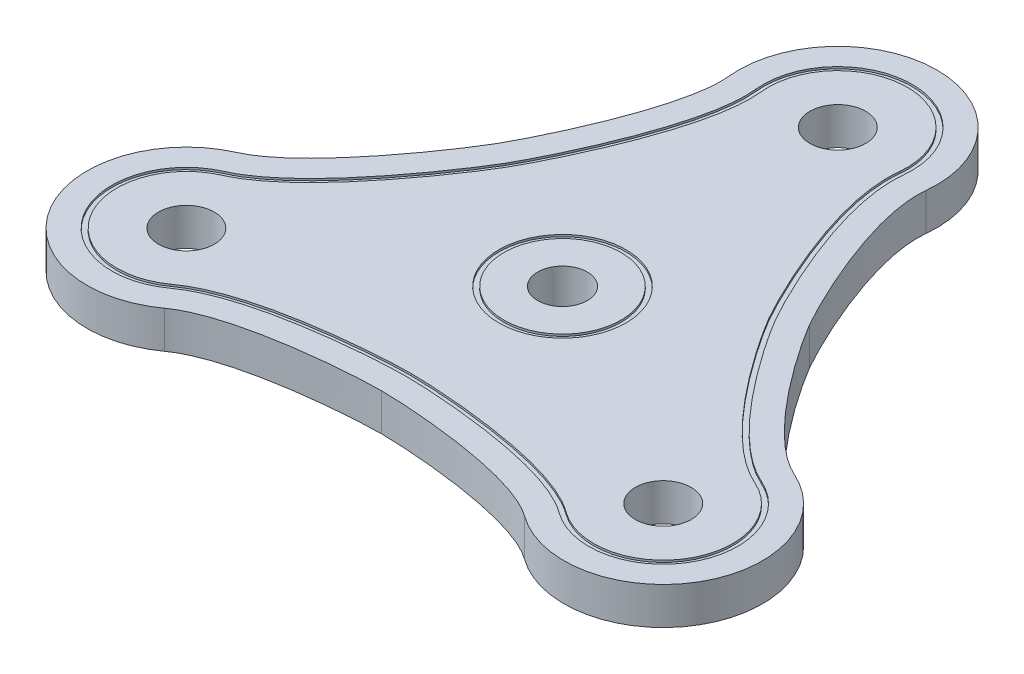
SolidWorks part; units mm, degrees
ref_plane "Front Plane" through (0, 0, 0) normal (0, 0, 1) x (1, 0, 0)
ref_plane "Top Plane" through (0, 0, 0) normal (0, 1, 0) x (1, 0, 0)
ref_plane "Right Plane" through (0, 0, 0) normal (1, 0, 0) x (0, 0, -1)
sketch "Sketch1" plane through (0, 0, 0) normal (0, 1, 0) x (1, 0, 0)
  line L0 (0, 35.2219) -> (0, 0) construction
  line L1 (0, 0) -> (-30.503, -17.6109) construction
  line L2 (0, 0) -> (30.503, -17.6109) construction
  line L3 (0, 35.2219) -> (0, 69.7598) construction
  line L4 (-30.503, -17.6109) -> (-60.4137, -34.8799) construction
  line L5 (30.503, -17.6109) -> (60.4137, -34.8799) construction
  line L6 (-30.503, -17.6109) -> (0, 35.2219) construction
  line L7 (0, 35.2219) -> (30.503, -17.6109) construction
  line L8 (30.503, -17.6109) -> (-30.503, -17.6109) construction
  line L9 (52.5001, -30.3109) -> (-52.5001, -30.3109)
  line L10 (-52.5001, -30.3109) -> (0, 60.6219)
  line L11 (0, 60.6219) -> (52.5001, -30.3109)
  circle A0 centre (-30.503, -17.6109) radius 7.1232 construction
  circle A1 centre (0, 35.2219) radius 7.1232 construction
  circle A2 centre (30.503, -17.6109) radius 7.1232 construction
  circle A3 centre (0, 0) radius 3.175
  dimension "D3" = 61.0061
  dimension "D5" = 6.35
  dimension "D1" = 120
  dimension "D2" = 120
  dimension "D4" = 12.7
extrude "Boss-Extrude1" add sketch "Sketch1" along normal blind 4.7752
fillet "Fillet1" radius 12.7 3 edges at (52.5001, 2.3876, 30.3109) (0, 2.3876, -60.6219) (-52.5001, 2.3876, 30.3109)
hole_wizard "1/4 Clearance Hole1" positions "Sketch5" profile "Sketch4" hole size "1/4" standard "ANSI Inch"
sketch "Sketch5" plane through (0, 4.7752, 0) normal (0, 1, 0) x (1, 0, 0)
  point P0 (0, 35.2219)
  point P3 (-30.503, -17.6109)
  point P6 (30.503, -17.6109)
sketch "Sketch4" plane through (0, 4.7752, -35.2219) normal (1, 0, 0) x (0, 0, 1)
  line L0 (0, 0) -> (0, 37.1978)
  line L1 (0, 37.1978) -> (3.5712, 35.052)
  line L2 (3.5712, 35.052) -> (3.5712, 0)
  line L5 (3.5712, 0) -> (0, 0)
  line L10 (0, 37.1978) -> (-3.5712, 35.052) construction
  line L11 (0, -6.35) -> (0, 107.95) construction
  dimension "Hole Dia." = 7.1425
  dimension "Hole Depth" = 35.052
  dimension "Drill Angle" = 118
ref_axis "Axis1" through (0, 12.9178, 0) along (0, -1, 0)
sketch "Sketch8" plane through (0, 0, 0) normal (0, 1, 0) x (1, 0, 0)
  line L0 (26.25, 15.1555) -> (20.0453, 11.5732) construction
  line L1 (0, 60.6219) -> (52.5001, -30.3109) construction
  line L2 (41.5015, -11.2609) -> (10.9985, 41.5719)
  circle A0 centre (0, 35.2219) radius 12.7
  arc A1 (10.9985, 41.5719) -> (-10.9985, 41.5719) centre (0, 35.2219) ccw construction
  circle A2 centre (30.503, -17.6109) radius 12.7
  spline S0 degree 3 poles (20.0453, 11.5732) (18.0567, 15.0175) (11.9581, 27.5448) (12.6294, 33.8846) knots 0 0 0 0 1 1 1 1
  spline S1 degree 3 poles (20.0453, 11.5732) (22.0339, 8.1288) (29.8336, -3.4164) (35.6596, -6.0049) knots 0 0 0 0 1 1 1 1
extrude "Cut-Extrude3" cut sketch "Sketch8" along normal through all contours L0 L2 A0 S0 | L2 L0 S1 A2 region at (29.081, 0, -4.4076) region at (18.3576, 0, -22.9811)
pattern_circular "CirPattern6" count 3 over 360 about axis through (0, 12.9178, 0) along (0, -1, 0) of "Cut-Extrude3"
sketch "Sketch9" plane through (0, 4.7752, 0) normal (0, 1, 0) x (1, 0, 0)
  arc A0 (9.472, 34.2189) -> (-9.472, 34.2189) centre (0, 35.2219) ccw
  arc A1 (-34.3705, -8.9064) -> (-24.8984, -25.3125) centre (-30.503, -17.6109) ccw
  arc A2 (24.8984, -25.3125) -> (34.3705, -8.9064) centre (30.503, -17.6109) ccw
  arc A3 (12.6294, 33.8846) -> (-12.6294, 33.8846) centre (0, 35.2219) ccw
  arc A4 (-35.6596, -6.0049) -> (-23.0302, -27.8797) centre (-30.503, -17.6109) ccw
  arc A5 (23.0302, -27.8797) -> (35.6596, -6.0049) centre (30.503, -17.6109) ccw
  arc A6 (12.6294, 33.8846) -> (-12.6294, 33.8846) centre (0, 35.2219) ccw construction
  arc A7 (-35.6596, -6.0049) -> (-23.0302, -27.8797) centre (-30.503, -17.6109) ccw construction
  arc A8 (23.0302, -27.8797) -> (35.6596, -6.0049) centre (30.503, -17.6109) ccw construction
  arc A9 (8.8406, 34.2858) -> (-8.8406, 34.2858) centre (0, 35.2219) ccw
  arc A10 (-34.1126, -9.4867) -> (-25.2721, -24.7991) centre (-30.503, -17.6109) ccw
  arc A11 (25.2721, -24.7991) -> (34.1126, -9.4867) centre (30.503, -17.6109) ccw
  circle A12 centre (0, 0) radius 7.4922
  circle A13 centre (0, 0) radius 8.1272
  spline S0 degree 1 poles (-9.472, 34.2189) (-17.2957, 9.9857) knots 0 0 1 1 construction
  spline S1 degree 1 poles (-17.2957, 9.9857) (-34.3705, -8.9064) knots 0 0 1 1 construction
  spline S2 degree 1 poles (-24.8984, -25.3125) (0, -19.9713) knots 0 0 1 1 construction
  spline S3 degree 1 poles (0, -19.9713) (24.8984, -25.3125) knots 0 0 1 1 construction
  spline S4 degree 1 poles (34.3705, -8.9064) (17.2957, 9.9857) knots 0 0 1 1 construction
  spline S5 degree 1 poles (17.2957, 9.9857) (9.472, 34.2189) knots 0 0 1 1 construction
  spline S6 degree 3 poles (-1302.6575, -1493.3617) (1264.2656, 1760.3115) (-1222.2453, -1769.2494) (1055.4921, 1697.5307) knots -4.35176 -4.35176 -4.35176 -4.35176 5.311596 5.311596 5.311596 5.311596 only from (-12.6294, 33.8846) to (-20.0453, 11.5732)
  spline S7 degree 3 poles (-942.3647, -1762.8603) (921.0943, 1943.1248) (-892.3396, -1975.0381) (641.9557, 1874.8036) knots -4.311607 -4.311607 -4.311607 -4.311607 5.35175 5.35175 5.35175 5.35175 only from (-20.0453, 11.5732) to (-35.6596, -6.0049)
  spline S8 degree 3 poles (1944.6179, -381.4536) (-2156.6073, 214.7304) (2143.3376, -173.8708) (-1997.8508, 65.3176) knots -4.35176 -4.35176 -4.35176 -4.35176 5.311596 5.311596 5.311596 5.311596 only from (-23.0302, -27.8797) to (0, -23.1463)
  spline S9 degree 3 poles (1997.8642, 65.3184) (-2143.3426, -173.8714) (2156.603, 214.7302) (-1944.6054, -381.4518) knots -4.311607 -4.311607 -4.311607 -4.311607 5.35175 5.35175 5.35175 5.35175 only from (0, -23.1463) to (23.0302, -27.8797)
  spline S10 degree 3 poles (-641.9604, 1874.8154) (892.3417, -1975.0419) (-921.0923, 1943.1202) (942.3587, -1762.8483) knots -4.35176 -4.35176 -4.35176 -4.35176 5.311596 5.311596 5.311596 5.311596 only from (35.6596, -6.0049) to (20.0453, 11.5732)
  spline S11 degree 3 poles (-1055.4995, 1697.5419) (1222.2483, -1769.2535) (-1264.2633, 1760.3078) (1302.6497, -1493.3518) knots -4.311607 -4.311607 -4.311607 -4.311607 5.35175 5.35175 5.35175 5.35175 only from (20.0453, 11.5732) to (12.6294, 33.8846)
  spline S12 degree 3 poles (-12.6294, 33.8846) (-11.9581, 27.5448) (-18.0567, 15.0175) (-20.0453, 11.5732) knots 0 0 0 0 1 1 1 1 construction
  spline S13 degree 3 poles (-20.0453, 11.5732) (-22.0339, 8.1288) (-29.8336, -3.4164) (-35.6596, -6.0049) knots 0 0 0 0 1 1 1 1 construction
  spline S14 degree 3 poles (-23.0302, -27.8797) (-17.8754, -24.1284) (-3.9772, -23.1463) (0, -23.1463) knots 0 0 0 0 1 1 1 1 construction
  spline S15 degree 3 poles (0, -23.1463) (3.9772, -23.1463) (17.8754, -24.1284) (23.0302, -27.8797) knots 0 0 0 0 1 1 1 1 construction
  spline S16 degree 3 poles (35.6596, -6.0049) (29.8336, -3.4164) (22.0339, 8.1288) (20.0453, 11.5732) knots 0 0 0 0 1 1 1 1 construction
  spline S17 degree 3 poles (20.0453, 11.5732) (18.0567, 15.0175) (11.9581, 27.5448) (12.6294, 33.8846) knots 0 0 0 0 1 1 1 1 construction
  spline S18 degree 3 poles (-9.472, 34.2189) (-9.3554, 33.1172) (-9.4289, 30.9191) (-10.0752, 27.4819) (-11.0973, 23.9595) (-12.3605, 20.4654) (-13.7396, 17.1479) (-14.8823, 14.664) (-15.7312, 12.9274) (-16.3214, 11.7688) (-16.7608, 10.9422) (-17.0807, 10.3623) (-17.2215, 10.1142) (-17.2957, 9.9857) knots 0 0 0 0 0.125 0.25 0.375 0.5 0.625 0.75 0.8125 0.875 0.9375 0.96875 1 1 1 1
  spline S19 degree 3 poles (-17.2957, 9.9857) (-17.3699, 9.8572) (-17.5144, 9.6112) (-17.8566, 9.0442) (-18.3528, 8.2503) (-19.0611, 7.1599) (-20.1405, 5.5564) (-21.7203, 3.3249) (-23.9038, 0.4718) (-26.2982, -2.3692) (-28.8376, -5.0156) (-31.4912, -7.2939) (-33.3581, -8.4566) (-34.3705, -8.9064) knots 0 0 0 0 0.03125 0.0625 0.125 0.1875 0.25 0.375 0.5 0.625 0.75 0.875 1 1 1 1
  spline S20 degree 3 poles (-24.8984, -25.3125) (-24.0027, -24.6606) (-22.0623, -23.6252) (-18.7624, -22.4663) (-15.2009, -21.5904) (-11.5433, -20.9372) (-7.9807, -20.4728) (-5.2583, -20.2204) (-3.3299, -20.0874) (-2.0314, -20.0192) (-1.0958, -19.9864) (-0.4337, -19.9735) (-0.1484, -19.9713) (0, -19.9713) knots 0 0 0 0 0.125 0.25 0.375 0.5 0.625 0.75 0.8125 0.875 0.9375 0.96875 1 1 1 1
  spline S21 degree 3 poles (0, -19.9713) (0.1484, -19.9713) (0.4337, -19.9735) (1.0958, -19.9864) (2.0314, -20.0192) (3.3299, -20.0874) (5.2583, -20.2204) (7.9807, -20.4728) (11.5433, -20.9372) (15.2009, -21.5904) (18.7624, -22.4663) (22.0623, -23.6252) (24.0027, -24.6606) (24.8984, -25.3125) knots 0 0 0 0 0.03125 0.0625 0.125 0.1875 0.25 0.375 0.5 0.625 0.75 0.875 1 1 1 1
  spline S22 degree 3 poles (34.3705, -8.9064) (33.3581, -8.4566) (31.4912, -7.2939) (28.8376, -5.0156) (26.2982, -2.3692) (23.9038, 0.4718) (21.7203, 3.3249) (20.1405, 5.5564) (19.0611, 7.1599) (18.3528, 8.2503) (17.8566, 9.0442) (17.5144, 9.6112) (17.3699, 9.8572) (17.2957, 9.9857) knots 0 0 0 0 0.125 0.25 0.375 0.5 0.625 0.75 0.8125 0.875 0.9375 0.96875 1 1 1 1
  spline S23 degree 3 poles (17.2957, 9.9857) (17.2215, 10.1142) (17.0807, 10.3623) (16.7608, 10.9422) (16.3214, 11.7688) (15.7312, 12.9274) (14.8823, 14.664) (13.7396, 17.1479) (12.3605, 20.4654) (11.0973, 23.9595) (10.0752, 27.4819) (9.4289, 30.9191) (9.3554, 33.1172) (9.472, 34.2189) knots 0 0 0 0 0.03125 0.0625 0.125 0.1875 0.25 0.375 0.5 0.625 0.75 0.875 1 1 1 1
  spline S24 degree 1 poles (16.7458, 9.6682) (8.8406, 34.2858) knots 0 0 1 1 construction
  spline S25 degree 1 poles (-8.8406, 34.2858) (-16.7458, 9.6682) knots 0 0 1 1 construction
  spline S26 degree 1 poles (-16.7458, 9.6682) (-34.1126, -9.4867) knots 0 0 1 1 construction
  spline S27 degree 1 poles (-25.2721, -24.7991) (0, -19.3363) knots 0 0 1 1 construction
  spline S28 degree 1 poles (0, -19.3363) (25.2721, -24.7991) knots 0 0 1 1 construction
  spline S29 degree 1 poles (34.1126, -9.4867) (16.7458, 9.6682) knots 0 0 1 1 construction
  spline S30 degree 3 poles (16.7458, 9.6682) (16.6701, 9.7992) (16.5262, 10.0528) (16.2019, 10.6408) (15.7578, 11.4762) (15.1629, 12.6442) (14.3079, 14.393) (13.1579, 16.893) (11.7688, 20.2345) (10.4939, 23.76) (9.4581, 27.3313) (8.796, 30.8326) (8.7191, 33.1387) (8.8406, 34.2858) knots 0 0 0 0 0.03125 0.0625 0.125 0.1875 0.25 0.375 0.5 0.625 0.75 0.875 1 1 1 1
  spline S31 degree 3 poles (-8.8406, 34.2858) (-8.7191, 33.1387) (-8.796, 30.8326) (-9.4581, 27.3313) (-10.4939, 23.76) (-11.7688, 20.2345) (-13.1579, 16.893) (-14.3079, 14.393) (-15.1629, 12.6442) (-15.7578, 11.4762) (-16.2019, 10.6408) (-16.5262, 10.0528) (-16.6701, 9.7992) (-16.7458, 9.6682) knots 0 0 0 0 0.125 0.25 0.375 0.5 0.625 0.75 0.8125 0.875 0.9375 0.96875 1 1 1 1
  spline S32 degree 3 poles (-16.7458, 9.6682) (-16.8214, 9.5371) (-16.9691, 9.2858) (-17.3161, 8.7108) (-17.8176, 7.9085) (-18.5316, 6.8093) (-19.6187, 5.1945) (-21.2087, 2.9485) (-23.408, 0.0748) (-25.8237, -2.792) (-28.3986, -5.4747) (-31.0998, -7.7987) (-33.0585, -9.0184) (-34.1126, -9.4867) knots 0 0 0 0 0.03125 0.0625 0.125 0.1875 0.25 0.375 0.5 0.625 0.75 0.875 1 1 1 1
  spline S33 degree 3 poles (-25.2721, -24.7991) (-24.3394, -24.1203) (-22.3038, -23.0338) (-18.9405, -21.8566) (-15.3298, -20.968) (-11.6392, -20.3093) (-8.0508, -19.8416) (-5.3107, -19.5875) (-3.3687, -19.4535) (-2.0598, -19.3848) (-1.1143, -19.3516) (-0.4428, -19.3385) (-0.1513, -19.3363) (0, -19.3363) knots 0 0 0 0 0.125 0.25 0.375 0.5 0.625 0.75 0.8125 0.875 0.9375 0.96875 1 1 1 1
  spline S34 degree 3 poles (0, -19.3363) (0.1513, -19.3363) (0.4428, -19.3385) (1.1143, -19.3516) (2.0598, -19.3848) (3.3687, -19.4535) (5.3107, -19.5875) (8.0508, -19.8416) (11.6392, -20.3093) (15.3298, -20.968) (18.9405, -21.8566) (22.3038, -23.0338) (24.3394, -24.1203) (25.2721, -24.7991) knots 0 0 0 0 0.03125 0.0625 0.125 0.1875 0.25 0.375 0.5 0.625 0.75 0.875 1 1 1 1
  spline S35 degree 3 poles (34.1126, -9.4867) (33.0585, -9.0184) (31.0998, -7.7987) (28.3986, -5.4747) (25.8237, -2.792) (23.408, 0.0748) (21.2087, 2.9485) (19.6187, 5.1945) (18.5316, 6.8093) (17.8176, 7.9085) (17.3161, 8.7108) (16.9691, 9.2858) (16.8214, 9.5371) (16.7458, 9.6682) knots 0 0 0 0 0.125 0.25 0.375 0.5 0.625 0.75 0.8125 0.875 0.9375 0.96875 1 1 1 1
  dimension "D4" = 0.635
  dimension "D1" = 0
  dimension "D2" = 3.175
  dimension "D3" = 3.81
extrude "Cut-Extrude4" cut sketch "Sketch9" against normal blind 0.254 contours S22 S23 A0 S18 S19 A1 S20 S21 A2 S35 A11 S34 S33 A10 S32 S31 A9 S30 | A13 A12 region at (11.8305, 4.7752, -21.6429) region at (-7.8973, 4.7752, 0)
